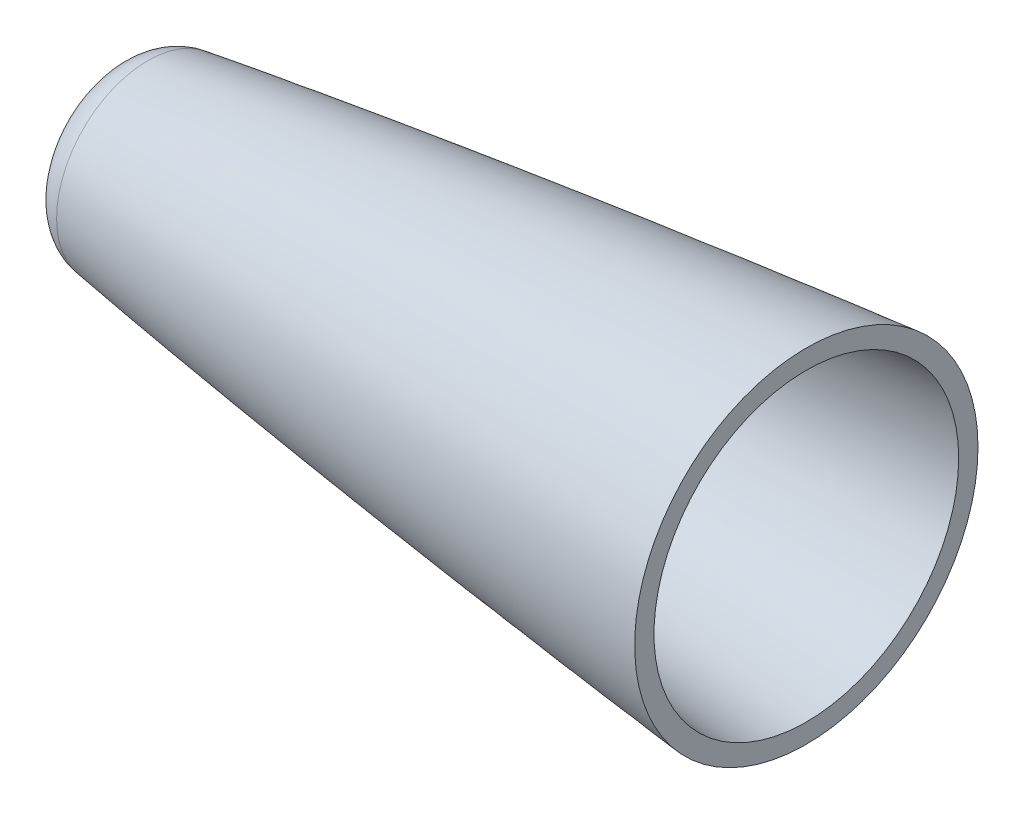
SolidWorks part; units mm, degrees
ref_plane "Front Plane" through (0, 0, 0) normal (0, 0, 1) x (1, 0, 0)
ref_plane "Top Plane" through (0, 0, 0) normal (0, 1, 0) x (1, 0, 0)
ref_plane "Right Plane" through (0, 0, 0) normal (1, 0, 0) x (0, 0, -1)
sketch "Sketch1" plane through (0, 0, 0) normal (0, 0, 1) x (1, 0, 0)
  line L2 (0, -76.2) -> (-921.7152, -76.2) construction
  line L3 (6.35, 6.35) -> (6.35, 0)
  line L4 (-259.8125, 11.4606) -> (6.35, 11.4606)
  line L5 (0, 0) -> (6.35, 0)
  line L6 (6.35, 6.35) -> (6.35, -76.2) construction
  line L7 (0, 0) -> (0, -76.2) construction
  line L8 (-921.7152, -58.5997) -> (-928.0652, -58.5997)
  line L9 (-928.0652, -58.5997) -> (-928.0652, -76.2) construction
  line L10 (-921.7152, -58.5997) -> (-921.7152, -76.2) construction
  line L11 (6.35, 11.4606) -> (6.35, 6.35)
  arc A0 (-254, 2.1118) -> (-248.4137, -0.891) centre (-248.6021, 5.4563) ccw
  arc A2 (-916.3053, -52.3197) -> (-921.7152, -58.5997) centre (-915.3652, -58.5997) ccw
  arc A4 (-254, 2.1118) -> (-259.6052, 5.114) centre (-259.3979, -1.2327) ccw
  arc A6 (-248.6021, 5.4563) -> (-248.6021, 5.4563) centre (-248.6021, 5.4563) ccw
  arc A7 (-248.6021, 5.4563) -> (-259.8125, 11.4606) centre (-259.3979, -1.2327) ccw
  arc A8 (-917.2454, -46.0396) -> (-928.0652, -58.5997) centre (-915.3652, -58.5997) ccw
  spline S0 degree 3 poles (0, 0) (-50.8, 0) (-101.6, 0) (-157.1824, 0) (-166.7471, 0) (-181.0943, 0) (-190.659, 0) (-199.5851, 0) (-207.8726, 0) (-220.3048, -0.155) (-228.5897, -0.3615) (-235.0947, -0.5237) (-239.8196, -0.6415) (-245.0466, -0.7915) (-247.9113, -0.876) (-248.4137, -0.891) knots 0.761574 0.761574 0.761574 0.761574 0.907842 0.907842 0.921611 0.935381 0.949151 0.949151 0.961082 0.973013 0.984944 0.984944 0.991748 0.998553 1 1 1 1
  spline S1 degree 1 poles (6.35, 6.35) (-248.6021, 5.4563) knots 0 0 1 1 construction
  spline S2 degree 3 poles (-259.6052, 5.114) (-267.1277, 4.8682) (-283.426, 4.2857) (-317.2703, 2.8805) (-361.13, 0.7112) (-431.2755, -3.372) (-501.3729, -8.2669) (-571.4145, -13.8917) (-623.9147, -18.4777) (-676.3803, -23.4393) (-728.8057, -28.7991) (-772.4536, -33.6275) (-807.3418, -37.7392) (-833.4907, -40.9589) (-859.6194, -44.3289) (-885.7239, -47.8693) (-904.6125, -50.5779) (-914.801, -52.0945) (-916.3053, -52.3197) knots 0.121539 0.121539 0.121539 0.121539 0.143123 0.168303 0.218664 0.269025 0.369746 0.420107 0.470467 0.520828 0.571189 0.62155 0.64673 0.67191 0.697091 0.722271 0.747451 0.751814 0.751814 0.751814 0.751814
  spline S3 degree 1 poles (-259.8125, 11.4606) (-917.2454, -46.0396) knots 0 0 1 1 construction
  spline S4 degree 3 poles (6.35, 6.35) (-14.881, 6.35) (-57.3424, 6.3506) (-110.4226, 6.3484) (-152.8795, 6.3528) (-179.4314, 6.3414) (-200.6356, 6.3648) (-216.6826, 6.282) (-232.6614, 5.8947) (-243.2867, 5.614) (-248.6021, 5.4563) knots 0.75548 0.75548 0.75548 0.75548 0.81661 0.87774 0.908305 0.93887 0.954152 0.969435 0.984717 1 1 1 1
  spline S5 degree 3 poles (-259.8125, 11.4606) (-287.3121, 10.5623) (-342.298, 8.1716) (-452.1401, 1.8335) (-589.2803, -8.5121) (-726.1766, -21.7709) (-835.4658, -34.5887) (-890.027, -41.9652) (-917.2454, -46.0396) knots 0.121539 0.121539 0.121539 0.121539 0.200324 0.279108 0.436676 0.594245 0.673029 0.751814 0.751814 0.751814 0.751814
revolve "Revolve1" add sketch "Sketch1" angle 360 about L2 region at (-124.3289, 8.8839, 0) region at (-3.0204, 3.175, 0)
ref_plane "Plane1" through (-438.15, 0, 0) normal (1, 0, 0) x (0, 0, -1)
sketch "Sketch8" plane through (-438.15, 0, 0) normal (1, 0, 0) x (0, 0, -1)
  circle A0 centre (0, -76.2) radius 87.6606 construction
  circle A1 centre (0, -76.2) radius 87.6606 construction
  circle A2 centre (0, -76.2) radius 142.3459
extrude "Cut-Extrude4" cut sketch "Sketch8" along normal through all
sketch "Sketch9" plane through (-438.15, 0, 0) normal (1, 0, 0) x (0, 0, -1)
  line L0 (0, 0) -> (0, -76.2) construction
  line L1 (0, -76.2) -> (23.926, -4.6927) construction
  circle A0 centre (0, -76.2) radius 72.2219 construction
  circle A1 centre (0, -76.2) radius 78.586 construction
  circle A2 centre (0, -76.2) radius 72.2219 construction
  circle A3 centre (0, -76.2) radius 78.586 construction
  circle A4 centre (0, -76.2) radius 75.4039 construction
  circle A5 centre (23.926, -4.6927) radius 2.286
  circle A6 centre (61.3875, -32.4127) radius 2.286
  circle A7 centre (75.4011, -76.858) radius 2.286
  circle A8 centre (60.614, -121.052) radius 2.286
  circle A9 centre (22.6744, -148.114) radius 2.286
  circle A10 centre (-23.926, -147.7073) radius 2.286
  circle A11 centre (-61.3875, -119.9873) radius 2.286
  circle A12 centre (-75.4011, -75.542) radius 2.286
  circle A13 centre (-60.614, -31.348) radius 2.286
  circle A14 centre (-22.6744, -4.286) radius 2.286
  point P31 (0, -76.2)
  dimension "D1" = 6.364
  dimension "D2" = 3.182
  dimension "D3" = 4.572
  dimension "D4" = 18.5
  dimension "D5" = 10
extrude "Cut-Extrude5" cut sketch "Sketch9" against normal blind 10.16
ref_plane "Plane3" through (-928.0652, 0, 0) normal (1, 0, 0) x (0, 0, -1)
sketch "Sketch10" plane through (-928.0652, 0, 0) normal (1, 0, 0) x (0, 0, -1)
  circle A0 centre (0, -76.2) radius 78.586 construction
  circle A1 centre (0, -76.2) radius 78.586 construction
  circle A2 centre (0, -76.2) radius 97.8804
ref_plane "Plane4" through (-699.4652, 0, 0) normal (1, 0, 0) x (0, 0, -1)
sketch "Sketch11" plane through (-699.4652, 0, 0) normal (1, 0, 0) x (0, 0, -1)
  circle A0 centre (0, -76.2) radius 97.8804 construction
  circle A1 centre (0, -76.2) radius 97.8804
extrude "Cut-Extrude7" cut sketch "Sketch11" along normal through all
